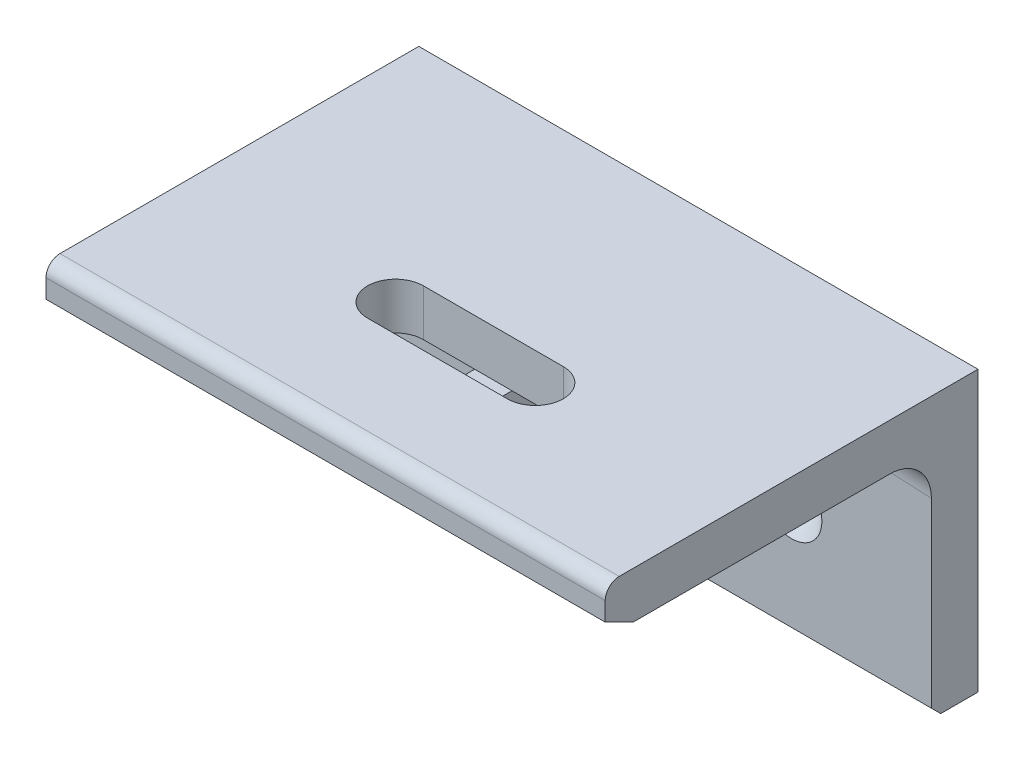
SolidWorks part; units mm, degrees
ref_plane "前视基准面" through (0, 0, 0) normal (0, 0, 1) x (1, 0, 0)
ref_plane "上视基准面" through (0, 0, 0) normal (0, 1, 0) x (1, 0, 0)
ref_plane "右视基准面" through (0, 0, 0) normal (1, 0, 0) x (0, 0, -1)
sketch "草图1" plane through (0, 0, 0) normal (0, 0, 1) x (1, 0, 0)
  line L0 (0, 0) -> (120, 0)
  line L1 (120, 0) -> (120, 60)
  line L2 (120, 60) -> (0, 60)
  line L3 (0, 60) -> (0, 0)
extrude "凸台-拉伸1" add sketch "草图1" along normal blind 10
ref_plane "基准面1" through (0, 50, 0) normal (0, 1, 0) x (1, 0, 0)
sketch "草图2" plane through (0, 50, 0) normal (0, 1, 0) x (1, 0, 0)
  line L0 (0, 0) -> (120, 0)
  line L1 (120, 0) -> (120, -80)
  line L2 (120, -80) -> (0, -80)
  line L3 (0, -80) -> (0, 0)
extrude "凸台-拉伸2" add sketch "草图2" along normal blind 10
ref_plane "基准面2" through (60, 0, 0) normal (1, 0, 0) x (0, 0, -1)
ref_plane "基准面3" through (120, 0, 0) normal (1, 0, 0) x (0, 0, -1)
ref_plane "基准面4" through (-1, 0, 0) normal (1, 0, 0) x (0, 0, -1)
sketch "草图10" plane through (0, 0, 0) normal (1, 0, 0) x (0, 0, -1)
  line L0 (-10, 50) -> (-10, 47)
  line L1 (-13, 50) -> (-10, 50)
  arc A0 (-10, 47) -> (-13, 50) centre (-13, 47) ccw
sketch "草图11" plane through (120, 0, 0) normal (1, 0, 0) x (0, 0, -1)
  line L0 (-10, 50) -> (-10, 41)
  line L1 (-19, 50) -> (-10, 50)
  arc A0 (-10, 41) -> (-19, 50) centre (-19, 41) ccw
loft "放样2" add profiles "草图10", "草图11"
ref_plane "基准面5" through (56, 0, 0) normal (1, 0, 0) x (0, 0, -1)
sketch "草图14" plane through (56, 0, 0) normal (1, 0, 0) x (0, 0, -1)
  line L0 (-10, 50) -> (-10, 10)
  line L1 (-10, 10) -> (-60, 50)
  line L2 (-60, 50) -> (-10, 50)
extrude "凸台-拉伸3" add sketch "草图14" along normal blind 8
ref_plane "基准面6" through (-0.5, 0, 0) normal (1, 0, 0) x (0, 0, -1)
sketch "草图17" plane through (-1, 0, 0) normal (1, 0, 0) x (0, 0, -1)
  line L0 (-80, 50) -> (-74, 50)
  line L1 (-74, 50) -> (-80, 53)
  line L2 (-80, 53) -> (-80, 50)
extrude "切除-拉伸13" cut sketch "草图17" along normal through all
fillet "圆角1" radius 3 1 edges at (60, 60, 80)
chamfer "倒角1" distance 2 angle 45 1 edges at (60, 0, 10)
ref_plane "基准面7" through (0, 0, 10) normal (0, 0, 1) x (1, 0, 0)
sketch "草图18" plane through (0, 0, 10) normal (0, 0, 1) x (1, 0, 0)
  circle A0 centre (30, 25) radius 6.5
  circle A1 centre (90, 25) radius 6.5
extrude "切除-拉伸14" cut sketch "草图18" against normal blind 3.2 draft 45
sketch "草图19" plane through (0, 0, 10) normal (0, 0, 1) x (1, 0, 0)
  circle A0 centre (30, 25) radius 3.3
  circle A1 centre (90, 25) radius 3.3
extrude "切除-拉伸15" cut sketch "草图19" against normal through all
ref_plane "基准面8" through (0, 60, 0) normal (0, 1, 0) x (1, 0, 0)
sketch "草图22" plane through (0, 60, 0) normal (0, 1, 0) x (1, 0, 0)
  line L0 (45, -44) -> (75, -44)
  line L1 (75, -56) -> (45, -56)
  arc A0 (75, -44) -> (75, -56) centre (75, -50) cw
  arc A1 (45, -56) -> (45, -44) centre (45, -50) cw
extrude "切除-拉伸19" cut sketch "草图22" against normal blind 10
